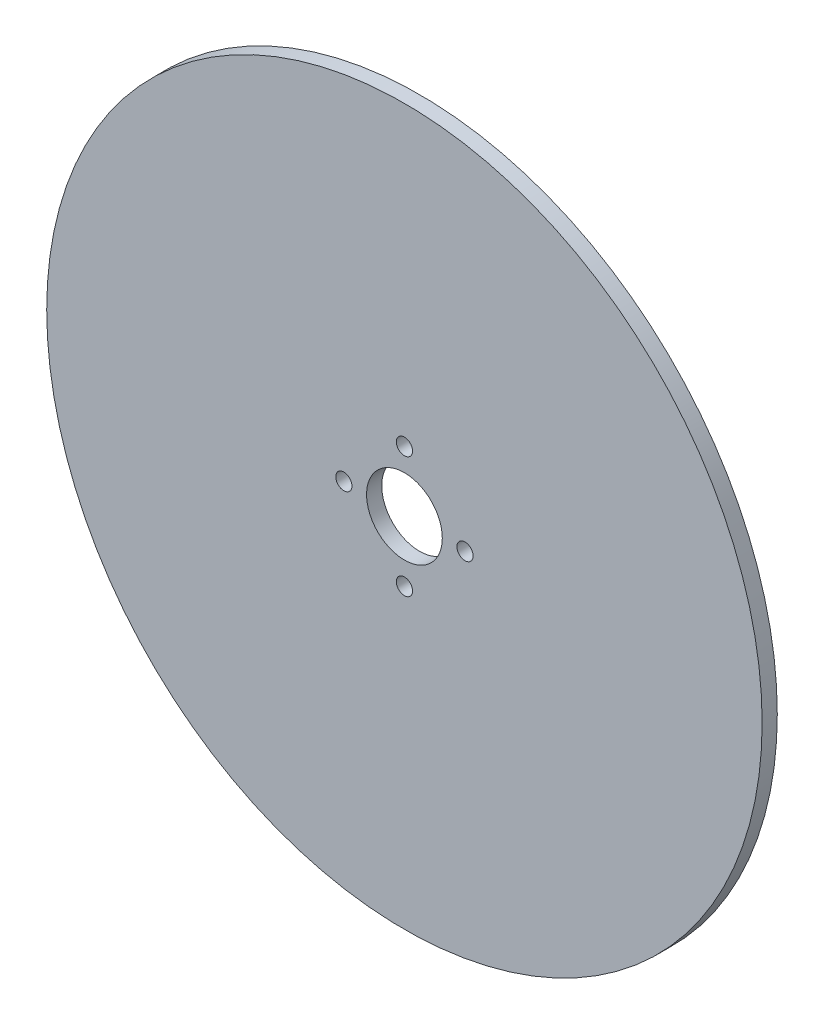
SolidWorks part; units mm, degrees
ref_plane "Front Plane" through (0, 0, 0) normal (0, 0, 1) x (1, 0, 0)
ref_plane "Top Plane" through (0, 0, 0) normal (0, 1, 0) x (1, 0, 0)
ref_plane "Right Plane" through (0, 0, 0) normal (1, 0, 0) x (0, 0, -1)
sketch "Sketch1" plane through (0, 0, 0) normal (0, 0, 1) x (1, 0, 0)
  circle A0 centre (0, 0) radius 75
  circle A1 centre (0, 0) radius 7.9375
  dimension "D1" = 150
  dimension "D2" = 15.875
extrude "Boss-Extrude1" add sketch "Sketch1" along normal blind 3.175
hole_wizard "M3 Clearance Hole1" positions "Sketch2" profile "Sketch3" hole size "M3" standard "ANSI Metric"
sketch "Sketch2" plane through (0, 0, 3.175) normal (0, 0, 1) x (1, 0, 0)
  point P0 (0, 12.7)
  point P2 (0, -12.7)
  point P4 (12.7, 0)
  point P6 (-12.7, 0)
  dimension "D1" = 12.7
  dimension "D2" = 12.7
  dimension "D3" = 12.7
  dimension "D4" = 12.7
sketch "Sketch3" plane through (0, 12.7, 3.175) normal (1, 0, 0) x (0, -1, 0)
  line L0 (0, 0) -> (0, 5.0215)
  line L1 (0, 5.0215) -> (1.7, 4)
  line L2 (1.7, 4) -> (1.7, 0)
  line L5 (1.7, 0) -> (0, 0)
  line L10 (0, 5.0215) -> (-1.7, 4) construction
  line L11 (0, -6.35) -> (0, 107.95) construction
  dimension "Hole Dia." = 3.4
  dimension "Hole Depth" = 4
  dimension "Drill Angle" = 118
